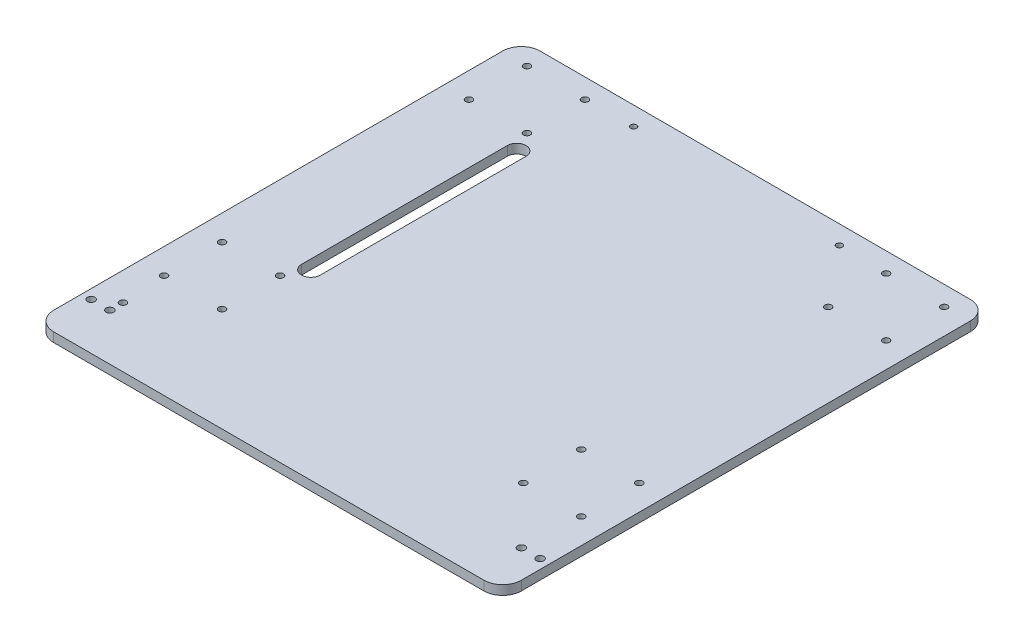
SolidWorks part; units mm, degrees
ref_plane "前视基准面" through (0, 0, 0) normal (0, 0, 1) x (1, 0, 0)
ref_plane "上视基准面" through (0, 0, 0) normal (0, 1, 0) x (1, 0, 0)
ref_plane "右视基准面" through (0, 0, 0) normal (1, 0, 0) x (0, 0, -1)
sketch "草图1" plane through (0, 0, 0) normal (0, 1, 0) x (1, 0, 0)
  line L0 (-125, 83) -> (-75, 83) construction
  line L1 (-125, -130) -> (125, -130)
  line L2 (-125, -130) -> (-125, 130)
  line L3 (-125, 130) -> (125, 130)
  line L4 (125, -130) -> (125, 130)
  line L5 (-125, -130) -> (125, 130) construction
  line L6 (-125, 130) -> (125, -130) construction
  line L7 (-125, -80) -> (-75, -80) construction
  line L8 (-125, -80) -> (-125, -38) construction
  line L9 (-125, -38) -> (-75, -38) construction
  line L10 (-75, -80) -> (-75, -38) construction
  line L11 (-117, -80) -> (-75, -80) construction
  line L12 (-117, -80) -> (-117, -38) construction
  line L13 (-117, -38) -> (-75, -38) construction
  line L14 (-75, -80) -> (-75, -38) construction
  line L15 (-117, -80) -> (-75, -38) construction
  line L16 (-117, -38) -> (-75, -80) construction
  line L17 (-111.5, -43.5) -> (-80.5, -43.5) construction
  line L18 (-111.5, -43.5) -> (-111.5, -74.5) construction
  line L19 (-111.5, -74.5) -> (-80.5, -74.5) construction
  line L20 (-80.5, -43.5) -> (-80.5, -74.5) construction
  line L21 (-125, 83) -> (-125, 125) construction
  line L22 (-125, 125) -> (-75, 125) construction
  line L23 (-75, 83) -> (-75, 125) construction
  line L24 (-117, 83) -> (-75, 83) construction
  line L25 (-117, 83) -> (-117, 125) construction
  line L26 (-117, 125) -> (-75, 125) construction
  line L27 (-75, 83) -> (-75, 125) construction
  line L28 (-117, 83) -> (-75, 125) construction
  line L29 (-117, 125) -> (-75, 83) construction
  line L30 (-111.5, 119.5) -> (-80.5, 119.5) construction
  line L31 (-111.5, 119.5) -> (-111.5, 88.5) construction
  line L32 (-111.5, 88.5) -> (-80.5, 88.5) construction
  line L33 (-80.5, 119.5) -> (-80.5, 88.5) construction
  line L34 (0, -130) -> (0, 130) construction
  line L35 (80.5, -43.5) -> (80.5, -74.5) construction
  line L36 (111.5, -74.5) -> (80.5, -74.5) construction
  line L37 (111.5, -43.5) -> (111.5, -74.5) construction
  line L38 (111.5, -43.5) -> (80.5, -43.5) construction
  line L39 (117, -38) -> (75, -80) construction
  line L40 (117, -80) -> (75, -38) construction
  line L41 (75, -80) -> (75, -38) construction
  line L42 (117, -38) -> (75, -38) construction
  line L43 (117, -80) -> (117, -38) construction
  line L44 (117, -80) -> (75, -80) construction
  line L45 (75, -80) -> (75, -38) construction
  line L46 (125, -38) -> (75, -38) construction
  line L47 (125, -80) -> (125, -38) construction
  line L48 (125, -80) -> (75, -80) construction
  line L49 (80.5, 119.5) -> (80.5, 88.5) construction
  line L50 (111.5, 88.5) -> (80.5, 88.5) construction
  line L51 (111.5, 119.5) -> (111.5, 88.5) construction
  line L52 (111.5, 119.5) -> (80.5, 119.5) construction
  line L53 (117, 125) -> (75, 83) construction
  line L54 (117, 83) -> (75, 125) construction
  line L55 (75, 83) -> (75, 125) construction
  line L56 (117, 125) -> (75, 125) construction
  line L57 (117, 83) -> (117, 125) construction
  line L58 (117, 83) -> (75, 83) construction
  line L59 (75, 83) -> (75, 125) construction
  line L60 (125, 125) -> (75, 125) construction
  line L61 (125, 83) -> (125, 125) construction
  line L62 (125, 83) -> (75, 83) construction
  line L63 (-75, 77.5) -> (-75, -32.5) construction
  line L64 (-70, 77.5) -> (-70, -32.5)
  line L65 (-80, 77.5) -> (-80, -32.5)
  circle A0 centre (-111.5, 119.5) radius 1.8
  circle A1 centre (-80.5, 119.5) radius 1.8
  circle A2 centre (-80.5, 88.5) radius 1.8
  circle A3 centre (-111.5, 88.5) radius 1.8
  circle A4 centre (-111.5, -43.5) radius 1.8
  circle A5 centre (-80.5, -43.5) radius 1.8
  circle A6 centre (-80.5, -74.5) radius 1.8
  circle A7 centre (-111.5, -74.5) radius 1.8
  circle A8 centre (111.5, -74.5) radius 1.8
  circle A9 centre (80.5, -74.5) radius 1.8
  circle A10 centre (80.5, -43.5) radius 1.8
  circle A11 centre (111.5, -43.5) radius 1.8
  circle A12 centre (111.5, 88.5) radius 1.8
  circle A13 centre (80.5, 88.5) radius 1.8
  circle A14 centre (80.5, 119.5) radius 1.8
  circle A15 centre (111.5, 119.5) radius 1.8
  circle A16 centre (-120, -105) radius 2
  circle A17 centre (-110, -105) radius 2
  circle A18 centre (110, -105) radius 2
  circle A19 centre (120, -105) radius 2
  circle A20 centre (-55, 120) radius 1.6
  circle A21 centre (55, 120) radius 1.6
  arc A22 (-70, 77.5) -> (-80, 77.5) centre (-75, 77.5) ccw
  circle A23 centre (-110, -98) radius 1.8
  arc A24 (-80, -32.5) -> (-70, -32.5) centre (-75, -32.5) ccw
  point P0 (0, 0)
  point P10 (-96, -59)
  point P22 (-96, 104)
  point P38 (-96, 104)
  point P45 (-96, -59)
  point P58 (96, -59)
  point P73 (96, 104)
  point P89 (-75, 22.5)
  dimension "D14" = 3.6
  dimension "D15" = 3.6
  dimension "D9" = 10
  dimension "D17" = 4
  dimension "D18" = 4
  dimension "D22" = 10
  dimension "D23" = 3.2
  dimension "D21" = 55
  dimension "D24" = 3.6
  dimension "D25" = 15
  dimension "D26" = 18
  dimension "D28" = 5
  dimension "D1" = 250
  dimension "D2" = 260
  dimension "D3" = 50
  dimension "D4" = 5
  dimension "D5" = 42
  dimension "D6" = 31
  dimension "D7" = 50
  dimension "D8" = 42
  dimension "D10" = 31
  dimension "D11" = 50
  dimension "D12" = 5
  dimension "D19" = 25
  dimension "D20" = 25
  dimension "D27" = 50
  dimension "D29" = 110
  dimension "D30" = 52.5
  dimension "D13" = 4
  dimension "D16" = 4
extrude "凸台-拉伸1" add sketch "草图1" along normal blind 5
fillet "圆角2" radius 10 4 edges at (125, 2.5, -130) (125, 2.5, 130) (-125, 2.5, -130) (-125, 2.5, 130)
